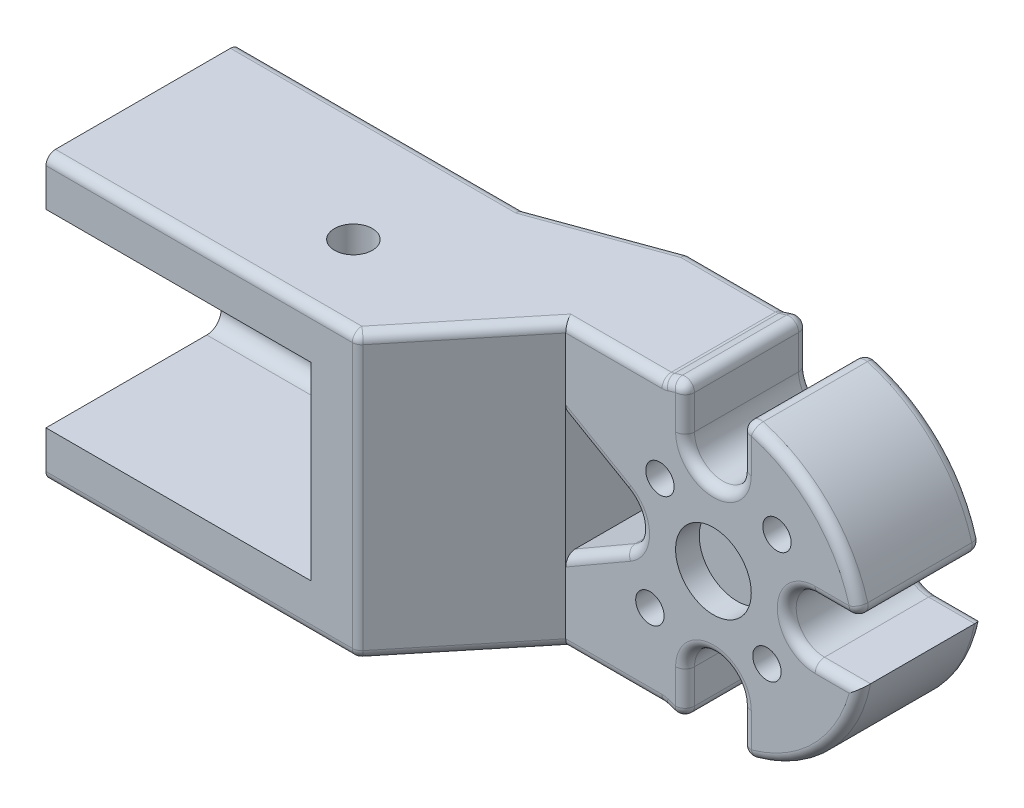
SolidWorks part; units mm, degrees
ref_plane "Plan de face" through (0, 0, 0) normal (0, 0, 1) x (1, 0, 0)
ref_plane "Plan de dessus" through (0, 0, 0) normal (0, 1, 0) x (1, 0, 0)
ref_plane "Plan de droite" through (0, 0, 0) normal (1, 0, 0) x (0, 0, -1)
sketch "Esquisse4" plane through (0, 0, 0) normal (0, 0, 1) x (1, 0, 0)
  line L0 (0, 0) -> (-6.7175, -6.7175) construction
  line L1 (0, 0) -> (6.7175, 6.7175) construction
  line L2 (0, 0) -> (2.9599, 0) construction
  line L3 (0, 0) -> (-3.5813, 0) construction
  line L4 (0, 0) -> (-5.6569, 5.6569) construction
  line L5 (0, 0) -> (5.6569, -5.6569) construction
  line L6 (-10.75, 3) -> (-13.5724, 3)
  line L7 (-10.75, -3) -> (-13.5724, -3)
  line L8 (3, 10.75) -> (3, 13.5724)
  line L9 (-3, 10.75) -> (-3, 13.5724)
  line L10 (10.75, -3) -> (13.5724, -3)
  line L11 (10.75, 3) -> (13.5724, 3)
  line L12 (-3, -10.75) -> (-3, -13.5724)
  line L13 (3, -10.75) -> (3, -13.5724)
  arc A0 (-13.5724, -3) -> (-3, -13.5724) centre (0, 0) ccw
  circle A1 centre (0, 0) radius 3.94
  circle A3 centre (-6.7175, -6.7175) radius 1.5
  circle A4 centre (6.7175, 6.7175) radius 1.5
  circle A5 centre (-5.6569, 5.6569) radius 1.5
  circle A6 centre (5.6569, -5.6569) radius 1.5
  arc A8 (-10.75, 3) -> (-10.75, -3) centre (-10.75, 0) cw
  arc A9 (3, 10.75) -> (-3, 10.75) centre (0, 10.75) cw
  arc A10 (-13.5724, -3) -> (-3, -13.5724) centre (0, 0) ccw
  arc A11 (10.75, -3) -> (10.75, 3) centre (10.75, 0) cw
  arc A12 (-13.5724, -3) -> (-3, -13.5724) centre (0, 0) ccw
  arc A13 (-3, -10.75) -> (3, -10.75) centre (0, -10.75) cw
  arc A14 (-13.5724, -3) -> (-3, -13.5724) centre (0, 0) ccw
  arc A15 (-3, 13.5724) -> (-13.5724, 3) centre (0, 0) ccw
  arc A16 (-3, 13.5724) -> (-13.5724, 3) centre (0, 0) ccw
  arc A17 (-3, 13.5724) -> (-13.5724, 3) centre (0, 0) ccw
  arc A18 (-3, 13.5724) -> (-13.5724, 3) centre (0, 0) ccw
  arc A19 (13.5724, 3) -> (3, 13.5724) centre (0, 0) ccw
  arc A20 (13.5724, 3) -> (3, 13.5724) centre (0, 0) ccw
  arc A21 (13.5724, 3) -> (3, 13.5724) centre (0, 0) ccw
  arc A22 (13.5724, 3) -> (3, 13.5724) centre (0, 0) ccw
  arc A23 (3, -13.5724) -> (13.5724, -3) centre (0, 0) ccw
  arc A24 (3, -13.5724) -> (13.5724, -3) centre (0, 0) ccw
  arc A25 (3, -13.5724) -> (13.5724, -3) centre (0, 0) ccw
  arc A26 (3, -13.5724) -> (13.5724, -3) centre (0, 0) ccw
  point P1 (7.75, 0)
  point P18 (-7.75, 0)
  point P42 (0, 0)
  dimension "D1" = 27.8
  dimension "D2" = 7.88
  dimension "D3" = 3
  dimension "D4" = 3
  dimension "D8" = 3
  dimension "D9" = 3
  dimension "D12" = 15.5
  dimension "D13" = 3
  dimension "D5" = 19
  dimension "D6" = 45
  dimension "D7" = 45
  dimension "D10" = 90
  dimension "D11" = 16
  dimension "D14" = 4
extrude "Boss.-Extru.3" add sketch "Esquisse4" along normal mid plane 13 contours L9 A15 L6 A8 A9 A5 | L11 A19 L8 A9 A11 A4 | L13 A23 L10 A11 A13 A6 | L12 A13 A8 L7 A0 A3 | A1 | A1 region at (-12.1612, 3.3839, 0) region at (0, 0, 0)
sketch "Esquisse20" plane through (0, 0, 6.5) normal (0, 0, 1) x (1, 0, 0)
  line L0 (-9.25, -2.5981) -> (-18.7195, -8.0653)
  line L1 (-18.7195, -8.0653) -> (-18.7195, 8.0653)
  line L2 (-18.7195, 8.0653) -> (-9.25, 2.5981)
  line L3 (7.952, 0) -> (17.2901, 0) construction
  line L4 (-7.75, 0) -> (-16.5433, 0) construction
  arc A0 (-9.25, -2.5981) -> (-9.25, 2.5981) centre (-10.75, 0) ccw
  arc A1 (-10.75, -3) -> (-10.75, 3) centre (-10.75, 0) ccw construction
  dimension "D1" = 60
extrude "Enlèv. mat.-Extru.7" cut sketch "Esquisse20" against normal through all contours L1 L2 A0 L0
sketch "Esquisse7" plane through (0, 0, 6.5) normal (0, 0, 1) x (1, 0, 0)
  line L0 (13.5724, 3) -> (15.6144, 3)
  line L1 (13.5724, -3) -> (15.6144, -3)
  line L2 (3, -13.5724) -> (3, -15.6144)
  line L3 (-3, -13.5724) -> (-3, -15.6144)
  line L4 (-13.5724, -3) -> (-15.6144, -3)
  line L5 (-13.5724, 3) -> (-15.6144, 3)
  line L6 (-3, 13.5724) -> (-3, 15.6144)
  line L7 (3, 13.5724) -> (3, 15.6144)
  arc A0 (-3, 15.6144) -> (-15.6144, 3) centre (0, 0) ccw
  arc A1 (-3, 13.5724) -> (-13.0482, 4.791) centre (0, 0) ccw construction
  arc A2 (13.5724, 3) -> (3, 13.5724) centre (0, 0) ccw
  arc A3 (-3, 13.5724) -> (-13.5724, 3) centre (0, 0) ccw
  arc A4 (-13.5724, -3) -> (-3, -13.5724) centre (0, 0) ccw
  arc A5 (3, -13.5724) -> (13.5724, -3) centre (0, 0) ccw
  arc A6 (15.6144, 3) -> (3, 15.6144) centre (0, 0) ccw
  arc A7 (3, -15.6144) -> (15.6144, -3) centre (0, 0) ccw
  arc A8 (-15.6144, -3) -> (-3, -15.6144) centre (0, 0) ccw
  point P27 (0, 0)
  dimension "D1" = 2
  dimension "D2" = 4
extrude "Boss.-Extru.7" add sketch "Esquisse7" against normal blind 13
ref_plane "Plan1" through (0, -15, 0) normal (0, 1, 0) x (1, 0, 0)
sketch "Esquisse6" plane through (0, -15, 0) normal (0, 1, 0) x (1, 0, 0)
  line L2 (-28.4061, 1.8442) -> (-58.4061, 1.8442)
  line L3 (-58.4061, 1.8442) -> (-58.4061, -22.1558)
  line L4 (-58.4061, -22.1558) -> (-28.4061, -22.1558)
  line L6 (-15.6144, -6.5) -> (-3, -6.5) construction
  line L7 (-9.3072, -6.5) -> (-15.6144, -6.5)
  line L11 (-28.4061, 1.8442) -> (-15.6144, 6.5)
  line L12 (-15.6144, 6.5) -> (-9.3072, 6.5)
  line L13 (-3, 6.5) -> (-15.6144, 6.5) construction
  line L16 (-9.3072, -6.5) -> (-3.3411, -6.5)
  line L19 (-15.6144, -6.5) -> (-28.4061, -22.1558)
  line L23 (-3.3411, -6.5) -> (-3.3411, 6.5)
  line L24 (-3.3411, 6.5) -> (-9.3072, 6.5)
  dimension "D1" = 24
  dimension "D2" = 30
  dimension "D3" = 230.749
  dimension "D4" = 13.6126
  dimension "D5" = 160
extrude "Boss.-Extru.8" add sketch "Esquisse6" along normal blind 30
hole_wizard "Trou taraudé M32" positions "Esquisse3D3" profile "Esquisse18" tap size "M3" standard "ISO" end condition up to next
sketch3d "Esquisse3D3"
  line L1 (5.6569, -5.6569, 6.5) -> (5.6569, -5.6569, -6.5) construction
  line L2 (6.7175, 6.7175, 6.5) -> (6.7175, 6.7175, -6.5) construction
  point P4 (5.6569, -5.6569, -6.5)
  point P8 (6.7175, 6.7175, -6.5)
  point P16 (0, 0, 0)
  point P17 (0, 0, 0)
sketch "Esquisse18" plane through (5.6569, -5.6569, -6.5) normal (1, 0, 0) x (0, 1, 0)
  line L0 (0, 0) -> (0, 28.6558)
  line L1 (0, 28.6558) -> (1.25, 28.6558)
  line L2 (1.25, 28.6558) -> (1.25, 0.5)
  line L3 (1.25, 0.5) -> (1.75, 0)
  line L5 (1.75, 0) -> (0, 0)
  line L6 (-1.25, 0.5) -> (-1.75, 0) construction
  line L11 (0, -6.35) -> (0, 107.95) construction
  dimension "Diamètre du trou pour taraudage jusqu'au prochain" = 2.5
  dimension "Profondeur du trou pour taraudage jusqu'au prochain" = 28.6558
  dimension "Diamètre du fraisage entrant" = 3.5
  dimension "Angle du fraisage entrant" = 90
sketch "Esquisse8" plane through (-58.4061, 0, 0) normal (-1, 0, 0) x (0, 0, 1)
  line L1 (18.6558, 10) -> (1.6558, 10)
  line L2 (20.1558, 8.5) -> (20.1558, -8.5)
  line L3 (18.6558, -10) -> (1.6558, -10)
  line L4 (0.1558, 8.5) -> (0.1558, -8.5)
  line L5 (20.1558, 10) -> (0.1558, -10) construction
  line L6 (20.1558, -10) -> (0.1558, 10) construction
  line L12 (22.1558, 15) -> (22.1558, -15) construction
  arc A0 (1.6558, 10) -> (0.1558, 8.5) centre (1.6558, 8.5) ccw
  arc A1 (1.6558, -10) -> (0.1558, -8.5) centre (1.6558, -8.5) cw
  arc A2 (20.1558, -8.5) -> (18.6558, -10) centre (18.6558, -8.5) cw
  arc A3 (18.6558, 10) -> (20.1558, 8.5) centre (18.6558, 8.5) cw
  point P0 (10.1558, 0)
  dimension "D4" = 1.5
  dimension "D1" = 20
  dimension "D2" = 20
  dimension "D3" = 2
extrude "Enlèv. mat.-Extru.1" cut sketch "Esquisse8" against normal blind 28
sketch "Esquisse22" plane through (0, 0, 6.5) normal (0, 0, 1) x (1, 0, 0)
  line L8 (-9.3072, -2.6311) -> (-9.25, -2.5981)
  line L10 (-9.3072, 2.6311) -> (-9.25, 2.5981)
  line L16 (-9.3072, -2.6311) -> (-15.6144, -6.2726)
  line L19 (-15.6144, 15) -> (-15.6144, -15) construction
  line L20 (-10.75, 0) -> (-13.1702, 0) construction
  line L21 (-9.3072, 2.6311) -> (-15.6144, 6.2726)
  line L22 (-15.6144, 6.2726) -> (-15.6144, -6.2726)
  arc A7 (-9.25, -2.5981) -> (-9.25, 2.5981) centre (-10.75, 0) ccw
  dimension "D1" = 60
  dimension "D2" = 3
  dimension "D3" = 7.2829
  dimension "D4" = 0.0661
extrude "Enlèv. mat.-Extru.8" cut sketch "Esquisse22" against normal through all contours L21 L16 region at (-12.4938, 0, 6.5)
sketch "Esquisse13" plane through (0, -15, 0) normal (0, -1, 0) x (1, 0, 0)
  line L0 (-28.4061, 10.1558) -> (-28.4061, -1.8442) construction
  line L1 (-28.4061, 10.1558) -> (-34.4061, 10.1558) construction
  circle A0 centre (-34.4061, 10.1558) radius 2
  point P5 (-34.4061, 10.1558)
  dimension "D3" = 4
  dimension "D1" = 12
  dimension "D2" = 6
extrude "Enlèv. mat.-Extru.4" cut sketch "Esquisse13" against normal through all
sketch "Esquisse15" plane through (0, 0, -1.8442) normal (0, 0, -1) x (-1, 0, 0)
  line L0 (28.4061, 15) -> (34.4061, 15) construction
  line L1 (28.4061, 15) -> (58.4061, 15) construction
  line L2 (34.4061, 15) -> (34.4061, 0) construction
  circle A1 centre (34.4061, 0) radius 2
  dimension "D2" = 4
  dimension "D1" = 15
  dimension "D3" = 6
extrude "Enlèv. mat.-Extru.5" cut sketch "Esquisse15" against normal through all
sketch "Esquisse16" plane through (-58.4061, 0, 0) normal (-1, 0, 0) x (0, 0, 1)
  line L0 (18.6558, 10) -> (18.6558, -10)
  line L1 (18.6558, -10) -> (18.6558, -15)
  line L2 (-1.8442, -15) -> (22.1558, -15) construction
  line L3 (18.6558, -15) -> (22.1558, -15)
  line L4 (22.1558, -15) -> (22.1558, 15)
  line L5 (22.1558, 15) -> (18.6558, 15)
  line L6 (-1.8442, 15) -> (22.1558, 15) construction
  line L7 (18.6558, 15) -> (18.6558, 10)
extrude "Enlèv. mat.-Extru.6" cut sketch "Esquisse16" against normal through all
sketch "Esquisse23" plane through (-30.4061, 0, 0) normal (-1, 0, 0) x (0, 0, 1)
  line L0 (1.5458, 1.92) -> (1.5458, 10.9402) construction
  line L1 (1.5458, 1.92) -> (1.5458, 0.29) construction
  line L2 (0.1558, 8.5) -> (0.1558, -8.5) construction
  line L3 (18.6558, 10) -> (1.6558, 10) construction
  line L4 (1.5458, 0.29) -> (1.5458, -1.34) construction
  circle A0 centre (1.5458, 1.92) radius 0.575
  circle A1 centre (1.5458, 0.29) radius 0.575
  circle A2 centre (1.5458, -1.34) radius 0.575
  dimension "D1" = 1.15
  dimension "D5" = 1.15
  dimension "D7" = 1.15
  dimension "D2" = 8.08
  dimension "D3" = 1.39
  dimension "D4" = 1.63
  dimension "D6" = 1.63
sketch "Esquisse24" plane through (0, 0, 6.5) normal (0, 0, 1) x (1, 0, 0)
  circle A0 centre (0, 0) radius 4
  dimension "D1" = 8
extrude "Enlèv. mat.-Extru.9" cut sketch "Esquisse24" against normal blind 2.5
extrude "Enlèv. mat.-Extru.11" cut sketch "Esquisse4<6>" against normal through all both and the other way through all contours A3 | A5
sketch "Esquisse4<6>" plane through (0, 0, 0) normal (0, 0, 1) x (1, 0, 0) same geometry as "Esquisse4"
fillet "Congé1" radius 1 52 edges at (-4.1482, -15.3494, -6.5) (-4.1482, 15.3494, -6.5) (-4.1482, 15.3494, 6.5) (3, 13.1822, 6.5) (-3, 13.1822, 6.5) (3, 13.1822, -6.5) (-3, 13.1822, -6.5) (13.1822, -3, 6.5) (13.1822, 3, 6.5) (13.1822, -3, -6.5) (13.1822, 3, -6.5) (-3, -13.1822, -6.5) (3, -13.1822, -6.5) (3, -13.1822, 6.5) (0, 7.75, 6.5) (0, 7.75, -6.5) (3, 15.6144, 0) (11.243, 11.243, -6.5) (15.6144, 3, 0) (11.243, 11.243, 6.5) (7.75, 0, 6.5) (7.75, 0, -6.5) (0, -7.75, 6.5) (0, -7.75, -6.5) (-43.4061, -15, -1.8442) (-22.0102, -15, -4.1721) (-10.444, -15, -6.5) (11.243, -11.243, -6.5) (11.243, -11.243, 6.5) (3, -15.6144, 0) (-3, -15.6144, 0) (-3, -13.1822, 6.5) (-4.1482, -15.3494, 6.5) (-5.2735, -15, 0) (-10.444, -15, 6.5) (-20.5804, -15, 12.5779) (-41.9762, -15, 18.6558) (-43.4061, 15, -1.8442) (-25.5464, 0, 18.6558) (-41.9762, 15, 18.6558) (-20.5804, 15, 12.5779) (-22.0102, 15, -4.1721) (-10.444, 15, -6.5) (-10.444, 15, 6.5) (-5.2735, 15, 0) (-3, 15.6144, 0) (-12.4322, -4.4353, -6.5) (-7.75, 0, -6.5) (-12.4322, 4.4353, 6.5) (-7.75, 0, 6.5) (-12.4322, 4.4353, -6.5) (-12.4322, -4.4353, 6.5)
